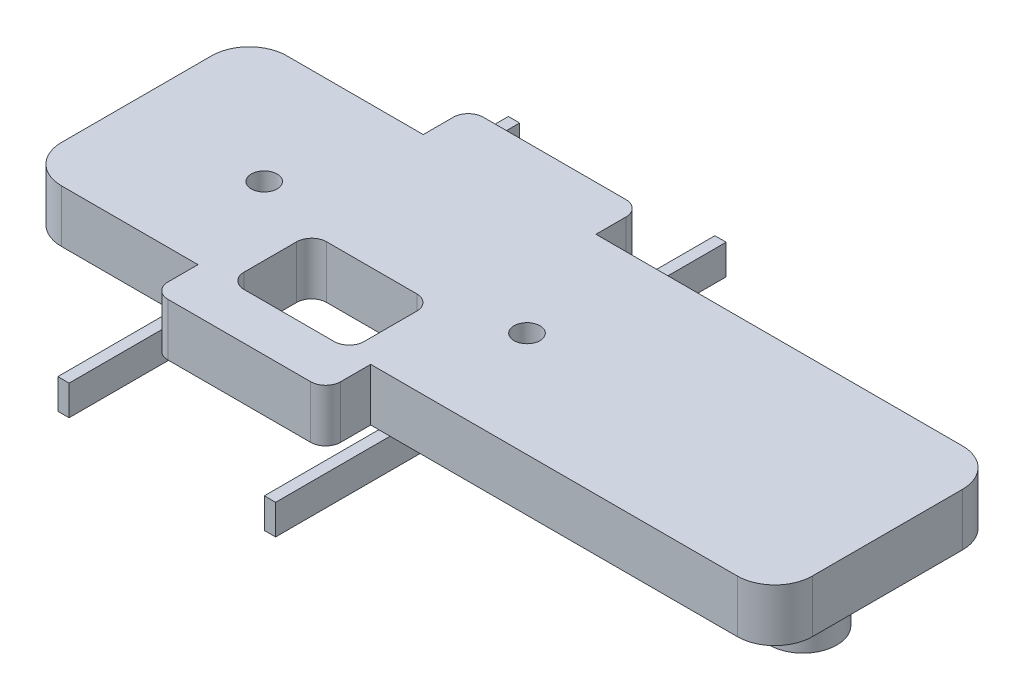
SolidWorks part; units mm, degrees
ref_plane "Front Plane" through (0, 0, 0) normal (0, 0, 1) x (1, 0, 0)
ref_plane "Top Plane" through (0, 0, 0) normal (0, 1, 0) x (1, 0, 0)
ref_plane "Right Plane" through (0, 0, 0) normal (1, 0, 0) x (0, 0, -1)
sketch "Sketch1" plane through (0, 0, 0) normal (0, 1, 0) x (1, 0, 0)
  line L1 (-45.1945, 17.8802) -> (54.8055, 17.8802)
  line L2 (-45.1945, 17.8802) -> (-45.1945, -12.1198)
  line L3 (-45.1945, -12.1198) -> (54.8055, -12.1198)
  line L4 (54.8055, 17.8802) -> (54.8055, -12.1198)
  dimension "D1" = 100
  dimension "D2" = 30
extrude "Boss-Extrude1" add sketch "Sketch1" along normal blind 7
ref_plane "Plane1" through (0, -1, 0) normal (0, -1, 0) x (-1, 0, 0)
sketch "Sketch2" plane through (0, -1, 0) normal (0, -1, 0) x (-1, 0, 0)
  line L0 (-54.8055, 2.8802) -> (57.5711, 2.8802) construction
  line L1 (-41.1646, -0.0198) -> (-44.5646, -0.0198)
  line L2 (-41.1646, -0.0198) -> (-41.1646, 5.7802)
  line L3 (-41.1646, 5.7802) -> (-44.5646, 5.7802)
  line L4 (-44.5646, -0.0198) -> (-44.5646, 5.7802)
  line L5 (-54.8055, -12.1198) -> (-54.8055, 17.8802) construction
  line L6 (-42.8646, -12.1198) -> (-42.8646, 27.765) construction
  line L8 (45.1945, -12.1198) -> (-54.8055, -12.1198) construction
  dimension "D1" = 3.4
  dimension "D2" = 5.8
  dimension "D3" = 1.7
  dimension "D4" = 2.9
extrude "Boss-Extrude2" add sketch "Sketch2" along normal blind 6 separate body
shell "Shell1" thickness 1 removed face at (42.8646, -7, -2.8802) outward yes
sketch "Sketch3" plane through (0, 0, 0) normal (0, -1, 0) x (-1, 0, 0)
  line L0 (-42.8646, -0.0198) -> (-42.8646, 11.0227) construction
  line L1 (-44.5646, -0.0198) -> (-41.1646, -0.0198) construction
  line L2 (-41.1646, 2.8802) -> (-49.8164, 2.8802) construction
  line L3 (-41.1646, -0.0198) -> (-41.1646, 5.7802) construction
  point P9 (-42.8646, 2.8802)
sketch "Sketch4" plane through (0, 0, 0) normal (0, -1, 0) x (-1, 0, 0)
  circle A0 centre (-42.9099, 3.5376) radius 4.5
  circle A1 centre (-42.9099, 3.5376) radius 3.7
extrude "Boss-Extrude3" add sketch "Sketch4" along normal blind 10
sketch "Sketch5" plane through (0, 0, 0) normal (0, -1, 0) x (-1, 0, 0)
  circle A0 centre (-42.8646, 2.8802) radius 4.25
  circle A1 centre (-42.8646, 2.8802) radius 5.5
extrude "Boss-Extrude4" add sketch "Sketch5" along normal blind 4
fillet "Fillet1" radius 5 4 edges at (-45.1945, 3.5, -17.8802) (-45.1945, 3.5, 12.1198) (54.8055, 3.5, -17.8802) (54.8055, 3.5, 12.1198)
sketch "Sketch6" plane through (0, 0, 0) normal (0, -1, 0) x (-1, 0, 0)
  line L0 (40.1945, -12.1198) -> (-49.8055, -12.1198) construction
  line L1 (22.0125, -12.1198) -> (-0.9875, -12.1198)
  line L2 (22.0125, -12.1198) -> (22.0125, -18.1198)
  line L3 (22.0125, -18.1198) -> (-0.9875, -18.1198)
  line L4 (-0.9875, -12.1198) -> (-0.9875, -18.1198)
  line L5 (45.1945, 2.8802) -> (44.2396, 2.8802) construction
  line L6 (45.1945, 12.8802) -> (45.1945, -7.1198) construction
  line L7 (22.0125, 23.8802) -> (-0.9875, 23.8802)
  line L8 (-0.9875, 17.8802) -> (-0.9875, 23.8802)
  line L9 (22.0125, 17.8802) -> (-0.9875, 17.8802)
  line L10 (22.0125, 17.8802) -> (22.0125, 23.8802)
  dimension "D1" = 6
  dimension "D2" = 23
extrude "Boss-Extrude5" add sketch "Sketch6" against normal up to surface (7 mm away) up to face at (4.8055, 7, -2.8802)
sketch "Sketch7" plane through (0, 0, 0) normal (0, -1, 0) x (-1, 0, 0)
  line L0 (40.1945, -12.1198) -> (22.0125, -12.1198) construction
  line L1 (-0.9875, -12.1198) -> (-49.8055, -12.1198) construction
  circle A0 centre (27.1973, 1.8802) radius 1.725
  circle A1 centre (-7.8027, 1.8802) radius 1.725
  dimension "D1" = 35
  dimension "D2" = 14
  dimension "D3" = 14
extrude "Cut-Extrude1" cut sketch "Sketch7" against normal up to surface (7 mm away) up to face at (-2.8535, 7, -2.8802)
fillet "Fillet2" radius 2 4 edges at (0.9875, 3.5, -23.8802) (-22.0125, 3.5, -23.8802) (0.9875, 3.5, 18.1198) (-22.0125, 3.5, 18.1198)
sketch "Sketch8" plane through (0, 0, 0) normal (0, -1, 0) x (-1, 0, 0)
  line L0 (1.0125, -18.1198) -> (20.0125, -18.1198) construction
  line L1 (18.0789, -11.9198) -> (2.0789, -11.9198)
  line L2 (18.0789, -11.9198) -> (18.0789, -0.9198)
  line L3 (18.0789, -0.9198) -> (2.0789, -0.9198)
  line L4 (2.0789, -11.9198) -> (2.0789, -0.9198)
  dimension "D1" = 16
  dimension "D2" = 11
  dimension "D3" = 6.2
extrude "Cut-Extrude2" cut sketch "Sketch8" against normal up to surface (7 mm away) up to face at (-27.1973, 7, -0.1552)
fillet "Fillet3" radius 2 4 edges at (-2.0789, 3.5, 0.9198) (-18.0789, 3.5, 0.9198) (-2.0789, 3.5, 11.9198) (-18.0789, 3.5, 11.9198)
sketch "Sketch9" plane through (0, 0, 0) normal (0, -1, 0) x (-1, 0, 0)
  line L0 (25.4321, 32.6336) -> (25.4321, -27.3664)
  line L1 (23.9321, 32.6336) -> (23.9321, -27.3664)
  line L2 (25.4321, -27.3664) -> (23.9321, -27.3664)
  line L3 (25.4321, 32.6336) -> (23.9321, 32.6336)
  line L6 (-3.5679, 32.6336) -> (-3.5679, -27.3664)
  line L7 (-3.5679, -27.3664) -> (-2.0679, -27.3664)
  line L8 (-2.0679, 32.6336) -> (-2.0679, -27.3664)
  line L9 (-3.5679, 32.6336) -> (-2.0679, 32.6336)
  dimension "D1" = 60
  dimension "D3" = 26
  dimension "D2" = 1.5
extrude "Boss-Extrude6" add sketch "Sketch9" along normal blind 4
